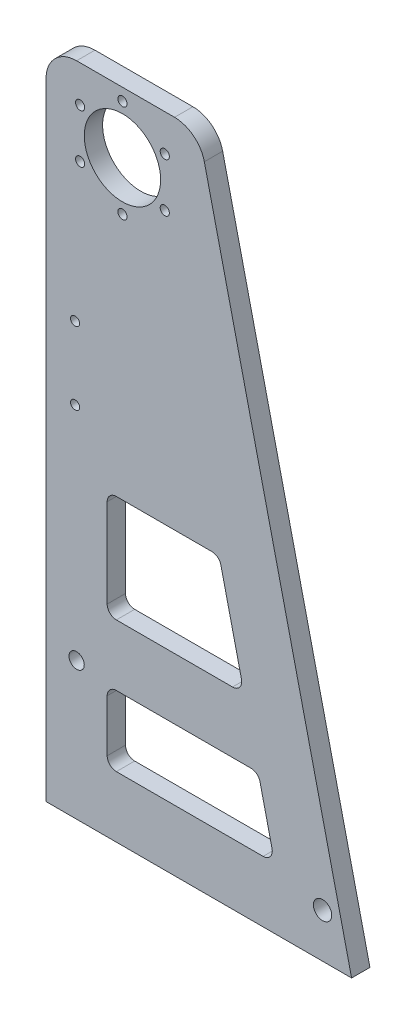
SolidWorks part; units mm, degrees
material "Policarbonato"
ref_plane "Plano frontal" through (0, 0, 0) normal (0, 0, 1) x (1, 0, 0)
ref_plane "Plano superior" through (0, 0, 0) normal (0, 1, 0) x (1, 0, 0)
ref_plane "Plano direito" through (0, 0, 0) normal (1, 0, 0) x (0, 0, -1)
sketch "Esboço1" plane through (0, 0, 0) normal (0, 0, 1) x (1, 0, 0)
  line L0 (0, 0) -> (0, 215)
  line L2 (100, 0) -> (0, 0)
  line L3 (0, 215) -> (50, 215)
  line L4 (50, 215) -> (100, 0)
  line L5 (10, 75.4302) -> (10, 15) construction
  line L6 (25, 215) -> (25, 175) construction
  line L7 (10, 15) -> (85.7122, 15) construction
  line L8 (85.7122, 15) -> (71.6586, 75.4302) construction
  line L9 (71.6586, 75.4302) -> (10, 75.4302) construction
  line L10 (20, 95) -> (20, 66)
  line L11 (23, 63) -> (61.0374, 63)
  line L12 (63.9594, 66.6795) -> (57.2152, 95.6795)
  line L13 (54.2932, 98) -> (23, 98)
  line L14 (20, 40) -> (20, 23)
  line L15 (23, 20) -> (71.0374, 20)
  line L16 (73.9594, 23.6795) -> (70.0059, 40.6795)
  line L17 (23, 43) -> (67.0839, 43)
  circle A0 centre (25, 195) radius 12.5
  circle A1 centre (25, 195) radius 16 construction
  circle A2 centre (25, 211) radius 1.5
  arc A8 (70.0059, 40.6795) -> (67.0839, 43) centre (67.0839, 40) ccw
  arc A9 (71.0374, 20) -> (73.9594, 23.6795) centre (71.0374, 23) ccw
  arc A10 (20, 23) -> (23, 20) centre (23, 23) ccw
  arc A11 (20, 40) -> (23, 43) centre (23, 40) cw
  arc A12 (57.2152, 95.6795) -> (54.2932, 98) centre (54.2932, 95) ccw
  arc A13 (61.0374, 63) -> (63.9594, 66.6795) centre (61.0374, 66) ccw
  arc A14 (20, 66) -> (23, 63) centre (23, 66) ccw
  arc A15 (20, 95) -> (23, 98) centre (23, 95) cw
  circle A16 centre (38.8564, 203) radius 1.5
  circle A17 centre (38.8564, 187) radius 1.5
  circle A18 centre (25, 179) radius 1.5
  circle A19 centre (11.1436, 187) radius 1.5
  circle A20 centre (11.1436, 203) radius 1.5
  circle A21 centre (10, 45) radius 2.5
  point P18 (25, 195)
  point P26 (22.5, 105)
  point P49 (20, 63)
  point P55 (25, 175)
  point P56 (25, 195)
  dimension "D3" = 20
  dimension "D4" = 25
  dimension "D6" = 32
  dimension "D7" = 3
  dimension "D21" = 3
  dimension "D15" = 10
  dimension "D16" = 45
  dimension "D17" = 5
  dimension "D1" = 215
  dimension "D2" = 100
  dimension "D5" = 50
  dimension "D9" = 25
  dimension "D10" = 6
  dimension "D11" = 20
  dimension "D12" = 20
  dimension "D13" = 15
  dimension "D14" = 20
  dimension "D18" = 10
  dimension "D20" = 20
  dimension "D22" = 23
  dimension "D8" = 35
extrude "Ressalto-extrusão2" add sketch "Esboço1" along normal blind 6
fillet "Filete1" radius 10 2 edges at (0, 215, 3) (50, 215, 3)
sketch "Esboço2" plane through (0, 0, 6) normal (0, 0, 1) x (1, 0, 0)
  circle A1 centre (90.5, 14.5) radius 3
  ellipse E2 centre (9.5, 117.2025) end of major axis (8, 117.2025) minor radius 1.4266
  ellipse E3 centre (9.5, 140.9789) end of major axis (8, 140.9789) minor radius 1.4266
extrude "Corte-extrusão1" cut sketch "Esboço2" against normal through all
